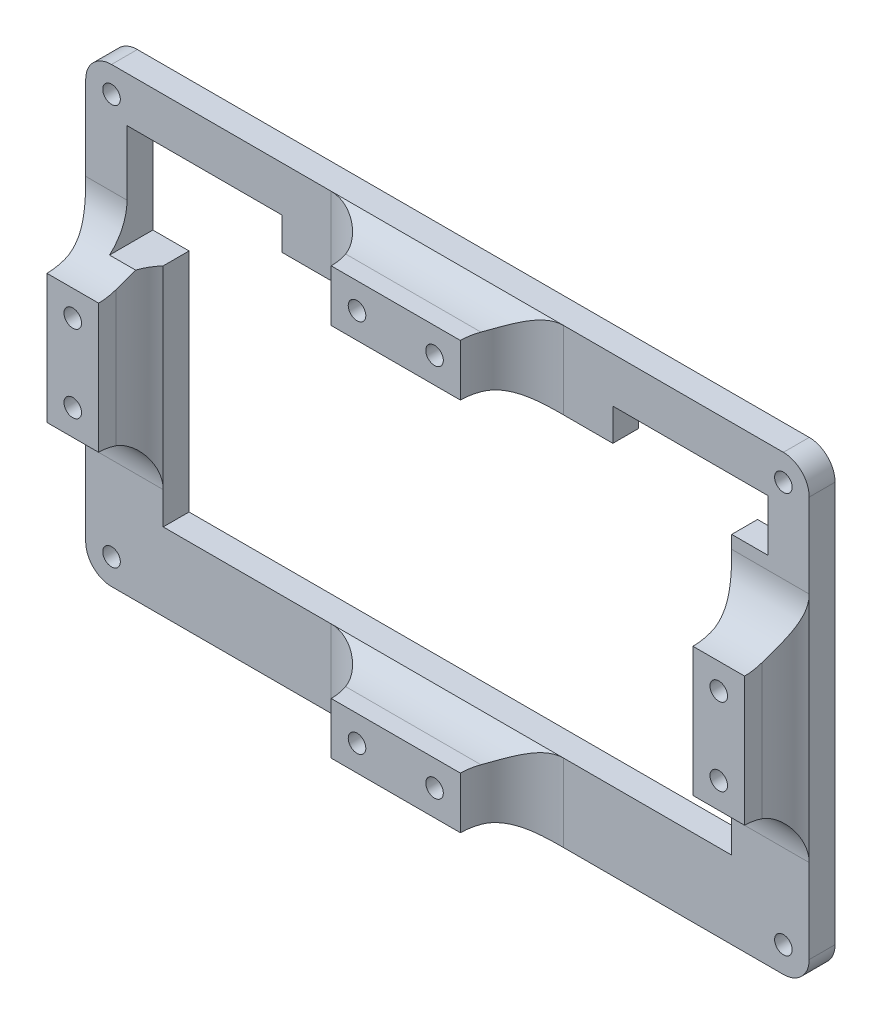
SolidWorks part; units mm, degrees
ref_plane "Front" through (0, 0, 0) normal (0, 0, 1) x (1, 0, 0)
ref_plane "Top" through (0, 0, 0) normal (0, 1, 0) x (1, 0, 0)
ref_plane "Right" through (0, 0, 0) normal (1, 0, 0) x (0, 0, -1)
sketch "Sketch1" plane through (0, 0, 0) normal (0, 0, 1) x (1, 0, 0)
  line L1 (-70, -43.75) -> (70, -43.75)
  line L2 (-70, -43.75) -> (-70, 43.75)
  line L3 (-70, 43.75) -> (70, 43.75)
  line L4 (70, -43.75) -> (70, 43.75)
  line L5 (-70, -43.75) -> (70, 43.75) construction
  line L6 (-70, 43.75) -> (70, -43.75) construction
  line L7 (-60, -33.75) -> (60, -33.75) construction
  line L8 (-60, -33.75) -> (-60, 33.75) construction
  line L9 (-60, 33.75) -> (60, 33.75) construction
  line L10 (60, -33.75) -> (60, 33.75) construction
  line L11 (-60, -33.75) -> (60, 33.75) construction
  line L12 (-60, 33.75) -> (60, -33.75) construction
  line L13 (55, -28.75) -> (-55, -28.75)
  line L14 (55, -28.75) -> (55, 28.75)
  line L15 (55, 28.75) -> (-55, 28.75)
  line L16 (-55, -28.75) -> (-55, 28.75)
  line L17 (55, -28.75) -> (-55, 28.75) construction
  line L18 (55, 28.75) -> (-55, -28.75) construction
  point P0 (0, 0)
  point P6 (0, 0)
  point P11 (0, 0)
  dimension "D1" = 87.5
  dimension "D2" = 140
  dimension "D3" = 67.5
  dimension "D4" = 120
  dimension "D5" = 57.5
  dimension "D6" = 110
extrude "Boss-Extrude1" add sketch "Sketch1" along normal blind 5
sketch "Sketch2" plane through (0, 0, 5) normal (0, 0, 1) x (1, 0, 0)
  line L1 (-65, -38.75) -> (65, -38.75) construction
  line L2 (-65, -38.75) -> (-65, 38.75) construction
  line L3 (-65, 38.75) -> (65, 38.75) construction
  line L4 (65, -38.75) -> (65, 38.75) construction
  line L5 (-65, -38.75) -> (65, 38.75) construction
  line L6 (-65, 38.75) -> (65, -38.75) construction
  point P0 (0, 0)
  dimension "D1" = 130
  dimension "D2" = 77.5
hole_wizard "M3 Clearance Hole1" positions "Sketch3" profile "Sketch4" hole size "M3" standard "ANSI Metric" end condition through all
sketch "Sketch3" plane through (0, 0, 5) normal (0, 0, 1) x (1, 0, 0)
  point P0 (-65, 38.75)
  point P3 (65, 38.75)
  point P6 (65, -38.75)
  point P9 (-65, -38.75)
sketch "Sketch4" plane through (-65, 38.75, 5) normal (1, 0, 0) x (0, -1, 0)
  line L0 (0, 0) -> (0, 5)
  line L1 (0, 5) -> (1.7, 5)
  line L2 (1.7, 5) -> (1.7, 0)
  line L5 (1.7, 0) -> (0, 0)
  line L11 (0, -6.35) -> (0, 107.95) construction
  dimension "Thru Hole Dia." = 3.4
  dimension "Thru Hole Depth" = 5
sketch "Sketch5" plane through (0, 0, 5) normal (0, 0, 1) x (1, 0, 0)
  line L0 (-60, 33.75) -> (60, 33.75) construction
  line L1 (-62, 35) -> (-32, 35)
  line L2 (-62, 35) -> (-62, 15)
  line L3 (-62, 15) -> (-32, 15)
  line L4 (-32, 35) -> (-32, 15)
  line L5 (-60, -33.75) -> (-60, 33.75) construction
  line L6 (60, -33.75) -> (60, 33.75) construction
  line L7 (62, 35) -> (32, 35)
  line L8 (62, 35) -> (62, 25)
  line L9 (62, 25) -> (32, 25)
  line L10 (32, 35) -> (32, 25)
  dimension "D1" = 30
  dimension "D2" = 20
  dimension "D3" = 1.25
  dimension "D4" = 2
  dimension "D5" = 30
  dimension "D6" = 10
  dimension "D7" = 2
  dimension "D8" = 1.25
extrude "Cut-Extrude1" cut sketch "Sketch5" against normal blind 5
fillet "Fillet1" radius 5 4 edges at (70, -43.75, 2.5) (70, 43.75, 2.5) (-70, -43.75, 2.5) (-70, 43.75, 2.5)
sketch "Sketch6" plane through (0, 0, 5) normal (0, 0, 1) x (1, 0, 0)
  line L1 (-62.5, -36.25) -> (62.5, -36.25) construction
  line L2 (-62.5, -36.25) -> (-62.5, 36.25) construction
  line L3 (-62.5, 36.25) -> (62.5, 36.25) construction
  line L4 (62.5, -36.25) -> (62.5, 36.25) construction
  line L5 (-62.5, -36.25) -> (62.5, 36.25) construction
  line L6 (-62.5, 36.25) -> (62.5, -36.25) construction
  line L8 (-12.5, 31.25) -> (12.5, 31.25)
  line L9 (-12.5, 31.25) -> (-12.5, 41.25)
  line L10 (-12.5, 41.25) -> (12.5, 41.25)
  line L11 (12.5, 31.25) -> (12.5, 41.25)
  line L12 (-12.5, 31.25) -> (12.5, 41.25) construction
  line L13 (-12.5, 41.25) -> (12.5, 31.25) construction
  line L14 (57.5, -12.5) -> (67.5, -12.5)
  line L15 (57.5, -12.5) -> (57.5, 12.5)
  line L16 (57.5, 12.5) -> (67.5, 12.5)
  line L17 (67.5, -12.5) -> (67.5, 12.5)
  line L18 (57.5, -12.5) -> (67.5, 12.5) construction
  line L19 (57.5, 12.5) -> (67.5, -12.5) construction
  line L20 (-67.5, -12.5) -> (-57.5, -12.5)
  line L21 (-67.5, -12.5) -> (-67.5, 12.5)
  line L22 (-67.5, 12.5) -> (-57.5, 12.5)
  line L23 (-57.5, -12.5) -> (-57.5, 12.5)
  line L24 (-67.5, -12.5) -> (-57.5, 12.5) construction
  line L25 (-67.5, 12.5) -> (-57.5, -12.5) construction
  line L26 (-12.5, -41.25) -> (12.5, -41.25)
  line L27 (-12.5, -41.25) -> (-12.5, -31.25)
  line L28 (-12.5, -31.25) -> (12.5, -31.25)
  line L29 (12.5, -41.25) -> (12.5, -31.25)
  line L30 (-12.5, -41.25) -> (12.5, -31.25) construction
  line L31 (-12.5, -31.25) -> (12.5, -41.25) construction
  point P0 (0, 0)
  point P6 (0, 36.25)
  point P11 (62.5, 0)
  point P16 (-62.5, 0)
  point P21 (0, -36.25)
  dimension "D1" = 72.5
  dimension "D2" = 125
  dimension "D3" = 25
  dimension "D4" = 10
  dimension "D5" = 25
  dimension "D6" = 10
  dimension "D7" = 25
  dimension "D8" = 10
  dimension "D9" = 25
  dimension "D10" = 10
extrude "Boss-Extrude2" add sketch "Sketch6" along normal blind 10
sketch "Sketch7" plane through (0, 0, 0) normal (0, 0, -1) x (-1, 0, 0)
  line L0 (-62.5, 7.5) -> (-62.5, -7.5) construction
  line L1 (-62.5, -36.25) -> (-62.5, 36.25) construction
  line L2 (-7.5, -36.25) -> (7.5, -36.25) construction
  line L3 (62.5, -36.25) -> (-62.5, -36.25) construction
  line L4 (62.5, 7.5) -> (62.5, -7.5) construction
  line L5 (62.5, -36.25) -> (62.5, 36.25) construction
  line L6 (-7.5, 36.25) -> (7.5, 36.25) construction
  line L7 (62.5, 36.25) -> (-62.5, 36.25) construction
  circle A0 centre (-62.5, 7.5) radius 1.7
  circle A1 centre (-62.5, -7.5) radius 1.7
  circle A2 centre (7.5, 36.25) radius 1.7
  circle A3 centre (-7.5, 36.25) radius 1.7
  circle A4 centre (62.5, 7.5) radius 1.7
  circle A5 centre (62.5, -7.5) radius 1.7
  circle A6 centre (7.5, -36.25) radius 1.7
  circle A7 centre (-7.5, -36.25) radius 1.7
  point P17 (-62.5, 0)
  point P19 (0, 36.25)
  point P21 (62.5, 0)
  point P23 (0, -36.25)
  dimension "D5" = 3.4
  dimension "D6" = 3.4
  dimension "D7" = 3.4
  dimension "D8" = 3.4
  dimension "D9" = 3.4
  dimension "D10" = 3.4
  dimension "D11" = 3.4
  dimension "D12" = 3.4
  dimension "D1" = 15
  dimension "D2" = 15
  dimension "D3" = 15
  dimension "D4" = 15
extrude "Cut-Extrude2" cut sketch "Sketch7" against normal through all
sketch "Sketch8" plane through (0, 0, 0) normal (0, 0, -1) x (-1, 0, 0)
  circle A0 centre (7.5, 36.25) radius 2.5
  circle A1 centre (-7.5, 36.25) radius 2.5
  circle A2 centre (62.5, 7.5) radius 2.5
  circle A3 centre (62.5, -7.5) radius 2.5
  circle A4 centre (7.5, -36.25) radius 2.5
  circle A5 centre (-7.5, -36.25) radius 2.5
  circle A6 centre (-62.5, 7.5) radius 2.5
  circle A7 centre (-62.5, -7.5) radius 2.5
  dimension "D1" = 5
  dimension "D2" = 5
  dimension "D3" = 5
  dimension "D4" = 5
  dimension "D5" = 5
  dimension "D6" = 5
  dimension "D7" = 5
  dimension "D8" = 5
extrude "Cut-Extrude3" cut sketch "Sketch8" against normal blind 10
fillet "Fillet2" radius 10 15 edges at (-57.5, 0, 5) (-67.5, 0, 5) (-62.5, -12.5, 5) (62.5, 12.5, 5) (57.5, 0, 5) (62.5, -12.5, 5) (67.5, 0, 5) (0, -31.25, 5) (12.5, -36.25, 5) (0, -41.25, 5) (-12.5, -36.25, 5) (-12.5, 36.25, 5) (0, 31.25, 5) (12.5, 36.25, 5) (0, 41.25, 5)
fillet "Fillet3" radius 10 1 edges at (-62.5, 12.5, 5)
